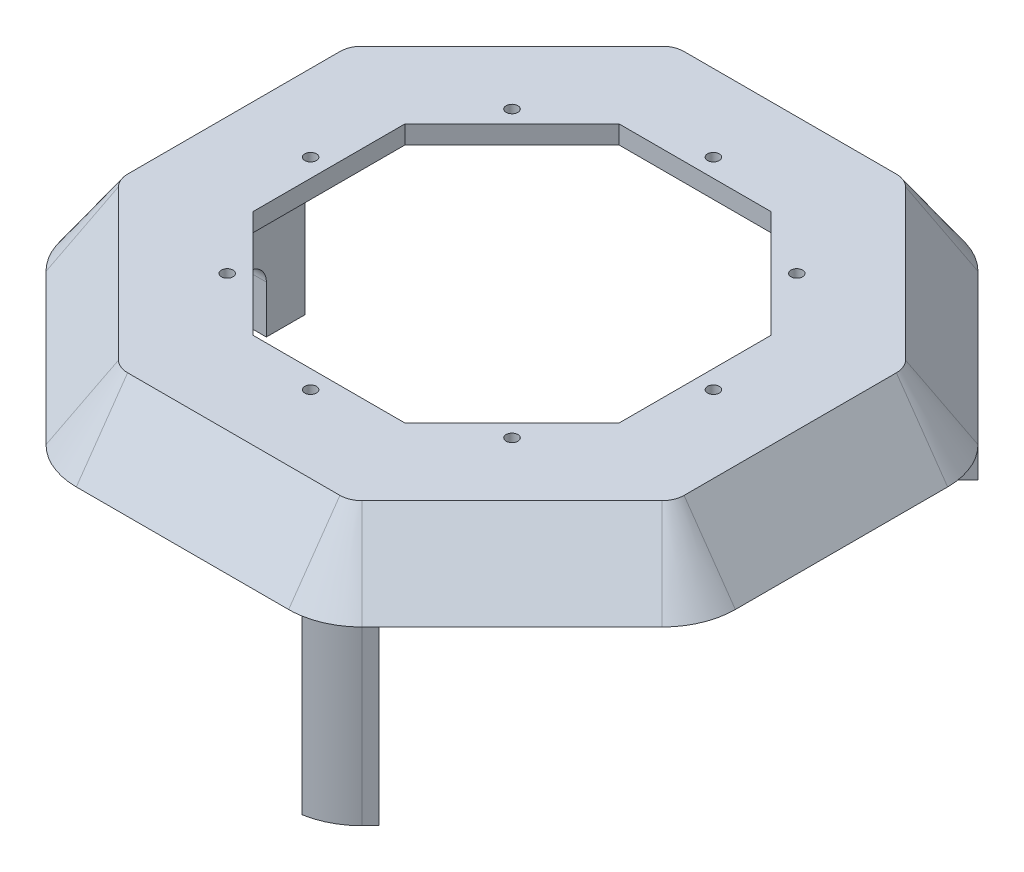
SolidWorks part; units mm, degrees
material "ABS"
ref_plane "Front Plane" through (0, 0, 0) normal (0, 0, 1) x (1, 0, 0)
ref_plane "Top Plane" through (0, 0, 0) normal (0, 1, 0) x (1, 0, 0)
ref_plane "Right Plane" through (0, 0, 0) normal (1, 0, 0) x (0, 0, -1)
sketch "Sketch1" plane through (0, 0, 0) normal (0, 1, 0) x (1, 0, 0)
  line L1 (90, -28.9949) -> (90, 28.9949)
  line L2 (84.1421, 43.1371) -> (43.1371, 84.1421)
  line L3 (28.9949, 90) -> (-28.9949, 90)
  line L4 (-43.1371, 84.1421) -> (-84.1421, 43.1371)
  line L5 (-90, 28.9949) -> (-90, -28.9949)
  line L6 (-84.1421, -43.1371) -> (-43.1371, -84.1421)
  line L7 (-28.9949, -90) -> (28.9949, -90)
  line L8 (43.1371, -84.1421) -> (84.1421, -43.1371)
  circle A0 centre (0, 0) radius 90 construction
  arc A1 (-90, -28.9949) -> (-84.1421, -43.1371) centre (-70, -28.9949) ccw
  arc A2 (-43.1371, -84.1421) -> (-28.9949, -90) centre (-28.9949, -70) ccw
  arc A3 (28.9949, -90) -> (43.1371, -84.1421) centre (28.9949, -70) ccw
  arc A4 (90, -28.9949) -> (84.1421, -43.1371) centre (70, -28.9949) cw
  arc A5 (90, 28.9949) -> (84.1421, 43.1371) centre (70, 28.9949) ccw
  arc A6 (43.1371, 84.1421) -> (28.9949, 90) centre (28.9949, 70) ccw
  arc A7 (-28.9949, 90) -> (-43.1371, 84.1421) centre (-28.9949, 70) ccw
  arc A8 (-84.1421, 43.1371) -> (-90, 28.9949) centre (-70, 28.9949) ccw
  dimension "D1" = 180
  dimension "D2" = 20
extrude "Initial extrude" add sketch "Sketch1" along normal blind 20
chamfer "Top chamfer" distance 20 angle 35 16 edges at (0, 20, 90) (-63.6396, 20, 63.6396) (-90, 20, 0) (-63.6396, 20, -63.6396) (0, 20, -90) (63.6396, 20, -63.6396) (90, 20, 0) (63.6396, 20, 63.6396) (-88.4776, 20, -36.6486) (-36.6486, 20, -88.4776) (36.6486, 20, -88.4776) (88.4776, 20, -36.6486) (88.4776, 20, 36.6486) (36.6486, 20, 88.4776) (-36.6486, 20, 88.4776) (-88.4776, 20, 36.6486) first distance on face at (0, 10, 90) first distance on face at (-63.6396, 10, 63.6396) first distance on face at (-90, 10, 0) first distance on face at (-63.6396, 10, -63.6396) first distance on face at (0, 10, -90) first distance on face at (63.6396, 10, -63.6396) first distance on face at (90, 10, 0) first distance on face at (63.6396, 10, 63.6396) first distance on face at (-87.7743, 10, -36.3573) first distance on face at (-36.3573, 10, -87.7743) first distance on face at (36.3573, 10, -87.7743) first distance on face at (87.7743, 10, -36.3573) first distance on face at (87.7743, 10, 36.3573) first distance on face at (36.3573, 10, 87.7743) first distance on face at (-36.3573, 10, 87.7743) first distance on face at (-87.7743, 10, 36.3573)
shell "Top shell" thickness 5 removed face at (0, 0, 0)
sketch "Sketch2" plane through (0, 20, 0) normal (0, 1, 0) x (1, 0, 0)
  line L1 (20.7107, 50) -> (-20.7107, 50)
  line L2 (-20.7107, 50) -> (-50, 20.7107)
  line L3 (-50, 20.7107) -> (-50, -20.7107)
  line L4 (-50, -20.7107) -> (-20.7107, -50)
  line L5 (-20.7107, -50) -> (20.7107, -50)
  line L6 (20.7107, -50) -> (50, -20.7107)
  line L7 (50, -20.7107) -> (50, 20.7107)
  line L8 (50, 20.7107) -> (20.7107, 50)
  circle A0 centre (0, 0) radius 50 construction
  dimension "D1" = 100
extrude "Interior hex hole" cut sketch "Sketch2" against normal through all
sketch "Sketch3" plane through (0, 15, 0) normal (0, -1, 0) x (1, 0, 0)
  line L0 (-50, -20.7107) -> (-50, 20.7107) construction
  circle A0 centre (-55, 0) radius 1.6
  circle A1 centre (-38.8909, 38.8909) radius 1.6
  circle A2 centre (0, 55) radius 1.6
  circle A3 centre (38.8909, 38.8909) radius 1.6
  circle A4 centre (55, 0) radius 1.6
  circle A5 centre (38.8909, -38.8909) radius 1.6
  circle A6 centre (0, -55) radius 1.6
  circle A7 centre (-38.8909, -38.8909) radius 1.6
  point P22 (0, 0)
  dimension "D1" = 3.2
  dimension "D2" = 5
  dimension "D3" = 8
extrude "Top screw holes" cut sketch "Sketch3" against normal through all
sketch "Sketch5" plane through (0, 0, 0) normal (0, -1, 0) x (1, 0, 0)
  line L3 (32.3551, -89.7157) -> (32.3551, -75)
  line L4 (36.8703, -73.1297) -> (45.5099, -81.7693)
  line L5 (30.8551, -79.9852) -> (30.8551, -83.4) construction
  line L6 (84.1421, -43.1371) -> (43.1371, -84.1421) construction
  line L7 (47.5919, -70.3536) -> (34.2983, -57.0599) construction
  line L8 (43.1371, -84.1421) -> (45.5099, -81.7693)
  circle A0 centre (35, -85) radius 1.6
  circle A7 centre (35, -75) radius 1.6 construction
  arc A9 (28.9949, -90) -> (43.1371, -84.1421) centre (28.9949, -70) ccw construction
  arc A10 (36.8703, -73.1297) -> (32.3551, -75) centre (35, -75) ccw
  circle A11 centre (35, -75) radius 1.6
  arc A14 (28.9949, -90) -> (43.1371, -84.1421) centre (28.9949, -70) ccw
  arc A15 (32.3551, -89.7157) -> (43.1371, -84.1421) centre (28.9949, -70) ccw
  dimension "D3" = 0
  dimension "D5" = 3.2
  dimension "D4" = 1.5
extrude "Boss-Extrude1" add sketch "Sketch5" along normal blind 47 and the other way up to next contours A11 | A0 | L4 L8 A15 L3 A10 region at (35, 0, -85) region at (35, 0, -75)
ref_plane "Plane1" through (0, 0, 0) normal (0, 0, -1) x (-1, 0, 0)
mirror "Mirror1" about plane through (0, 0, 0) normal (0, 0, -1) of "Boss-Extrude1"
sketch "Sketch6" plane through (0, 0, 0) normal (0, -1, 0) x (1, 0, 0)
  line L0 (-90, -28.9949) -> (-90, 28.9949) construction
  line L1 (-90, -28.9949) -> (-85.5, -28.9949)
  line L2 (-90, -28.9949) -> (-90, 28.9949)
  line L3 (-90, 28.9949) -> (-85.5, 28.9949)
  line L4 (-85.5, -28.9949) -> (-85.5, 28.9949)
  dimension "D1" = 4.5
extrude "Boss-Extrude2" add sketch "Sketch6" along normal blind 29
sketch "Sketch7" plane through (0, -29, 0) normal (0, -1, 0) x (1, 0, 0)
  line L0 (-90, 28.9949) -> (-90, -28.9949) construction
  line L1 (-90, -2.2382) -> (-85.5, -2.2382)
  line L2 (-90, -2.2382) -> (-90, 12.7618)
  line L3 (-90, 12.7618) -> (-85.5, 12.7618)
  line L4 (-85.5, -2.2382) -> (-85.5, 12.7618)
  line L6 (-85.5, -28.9949) -> (-85.5, 28.9949) construction
  line L8 (-90, -18.4069) -> (-85.5, -18.4069)
  line L9 (-90, -18.4069) -> (-90, -28.9949)
  line L10 (-90, -28.9949) -> (-85.5, -28.9949)
  line L11 (-85.5, -18.4069) -> (-85.5, -28.9949)
  line L12 (-84.1603, -16.3069) -> (-90.5103, -16.3069) construction
  line L13 (-87.5639, -4.3054) -> (-90.5103, -4.3054) construction
  line M3 (-90, 28.9949) -> (-90, -28.9949)
  line M4 (-90, -28.9949) -> (-85.5, -28.9949)
  line M5 (-85.5, -28.9949) -> (-85.5, 28.9949)
  dimension "D1" = 15
  dimension "D2" = 2.1
  dimension "D3" = 2.0672
extrude "Boss-Extrude3" add sketch "Sketch7" along normal blind 18 contours L8 M3 M4 M5 | L3 L4 L1 L2 region at (-87.75, -29, -23.7009)
ref_plane "Plane2" through (0, 0, 0) normal (0, 1, 0) x (1, 0, 0)
sketch "Sketch9" plane through (0, 0, 0) normal (0, 1, 0) x (1, 0, 0)
  line L1 (-85.5, 3.75) -> (-62.5, 3.75)
  line L2 (-85.5, 3.75) -> (-85.5, -3.75)
  line L3 (-85.5, -3.75) -> (-62.5, -3.75)
  line L4 (-62.5, 3.75) -> (-62.5, -3.75)
  line L6 (-85.5, 2.2382) -> (-85.5, -12.7618) construction
  point P4 (-85.5, 0)
  point P5 (0, 0)
  dimension "D1" = 23
  dimension "D2" = 7.5
extrude "Boss-Extrude4" add sketch "Sketch9" along normal up to next and the other way blind 20 contours L4 L3 L2 L1
sketch "Sketch10" plane through (0, 0, 3.75) normal (0, 0, 1) x (1, 0, 0)
  line L0 (-85.5, -20) -> (-62.5, 15)
  line L1 (-85.5, -20) -> (-62.5, -20) construction
  line L2 (-62.5, -20) -> (-62.5, 15) construction
  line L5 (-85.5, -20) -> (-62.5, -20)
  line L6 (-62.5, -20) -> (-62.5, 15)
  line L7 (-85.5, -29) -> (-85.5, 0) construction
  line L8 (-72.3992, 15) -> (-31.3942, 15) construction
  point P4 (-85.5, -15)
  point P7 (-65.5, 15)
extrude "Cut-Extrude1" cut sketch "Sketch10" against normal up to next contours L5 L6 L0
sketch "Sketch13" plane through (0, 0, 3.75) normal (0, 0, 1) x (1, 0, 0)
  line L0 (-85.5, 0) -> (-85.5, -6.4843)
  line L1 (-85.5, -20) -> (-85.5, 0) construction
  line L2 (-85.5, -6.4843) -> (-83.8961, 0)
  line L3 (-84.1421, 0) -> (-43.1371, 0) construction
  line L4 (-83.8961, 0) -> (-85.5, 0)
  point P5 (-83.8961, 0)
extrude "Boss-Extrude6" add sketch "Sketch13" along normal up to surface and the other way up to surface up to face at (-87.75, -14.5, 28.9949) other way up to face at (-87.75, -23.5, -28.9949)
fillet "Fillet1" radius 5 3 edges at (-87.75, -29, 12.7618) (-87.75, -29, -2.2382) (-87.75, -29, -18.4069)
